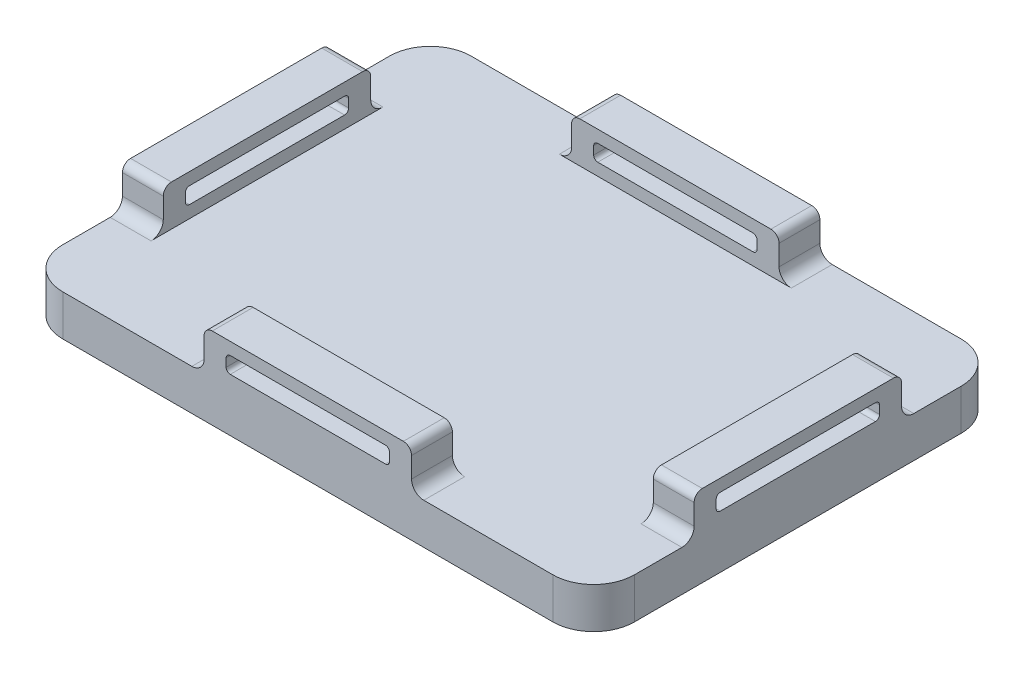
SolidWorks part; units mm, degrees
ref_plane "Front Plane" through (0, 0, 0) normal (0, 0, 1) x (1, 0, 0)
ref_plane "Top Plane" through (0, 0, 0) normal (0, 1, 0) x (1, 0, 0)
ref_plane "Right Plane" through (0, 0, 0) normal (1, 0, 0) x (0, 0, -1)
sketch "Sketch1" plane through (0, 0, 0) normal (0, 1, 0) x (1, 0, 0)
  line L1 (5, 0) -> (65, 0)
  line L2 (0, 5) -> (0, 45)
  line L3 (5, 50) -> (65, 50)
  line L4 (70, 5) -> (70, 45)
  arc A0 (5, 0) -> (0, 5) centre (5, 5) cw
  arc A1 (65, 0) -> (70, 5) centre (65, 5) ccw
  arc A2 (65, 50) -> (70, 45) centre (65, 45) cw
  arc A3 (0, 45) -> (5, 50) centre (5, 45) cw
  point P7 (0, 0)
  point P10 (70, 0)
  point P13 (70, 50)
  dimension "D3" = 5
  dimension "D1" = 70
  dimension "D2" = 50
extrude "Boss-Extrude1" add sketch "Sketch1" along normal blind 5
sketch "Sketch2" plane through (0, 0, 0) normal (0, -1, 0) x (1, 0, 0)
  line L0 (12, -25) -> (15, -25) construction
  line L1 (12, -19) -> (15, -19)
  line L2 (12, -19) -> (12, -31)
  line L3 (12, -31) -> (15, -31)
  line L4 (15, -19) -> (15, -31)
  line L5 (46, -23.5) -> (58, -23.5)
  line L6 (46, -23.5) -> (46, -26.5)
  line L7 (46, -26.5) -> (58, -26.5)
  line L8 (58, -23.5) -> (58, -26.5)
  line L9 (46, -25) -> (58, -25) construction
  line L10 (0, -25) -> (70, -25) construction
  line L11 (0, -45) -> (0, -5) construction
  line L12 (70, -5) -> (70, -45) construction
  dimension "D1" = 12
  dimension "D2" = 3
  dimension "D3" = 12
  dimension "D4" = 3
  dimension "D5" = 12
  dimension "D6" = 12
extrude "Boss-Extrude2" add sketch "Sketch2" along normal blind 10
sketch "Sketch3" plane through (0, 5, 0) normal (0, 1, 0) x (1, 0, 0)
  line L0 (0, 45) -> (0, 5) construction
  line L1 (5, 37.7) -> (0, 37.7)
  line L2 (5, 37.7) -> (5, 12.3)
  line L3 (5, 12.3) -> (0, 12.3)
  line L4 (0, 37.7) -> (0, 12.3)
  line L5 (70, 5) -> (70, 45) construction
  line L6 (70, 37.7) -> (65, 37.7)
  line L7 (70, 37.7) -> (70, 12.3)
  line L8 (70, 12.3) -> (65, 12.3)
  line L9 (65, 37.7) -> (65, 12.3)
  line L10 (0, 25) -> (5, 25) construction
  line L11 (65, 25) -> (70, 25) construction
  line L12 (0, 25) -> (70, 25) construction
  line L13 (65, 50) -> (5, 50) construction
  line L14 (22.3, 50) -> (47.7, 50)
  line L15 (22.3, 50) -> (22.3, 45)
  line L16 (22.3, 45) -> (47.7, 45)
  line L17 (47.7, 50) -> (47.7, 45)
  line L18 (5, 0) -> (65, 0) construction
  line L19 (22.3, 0) -> (47.7, 0)
  line L20 (22.3, 0) -> (22.3, 5)
  line L21 (22.3, 5) -> (47.7, 5)
  line L22 (47.7, 0) -> (47.7, 5)
  line L23 (35, 50) -> (35, 0) construction
  line L24 (35, 5) -> (35, 0) construction
  line L25 (35, 50) -> (35, 45) construction
  dimension "D1" = 25.4
  dimension "D2" = 5
  dimension "D3" = 5
  dimension "D4" = 25.4
  dimension "D5" = 25.4
  dimension "D6" = 25.4
  dimension "D7" = 5
  dimension "D8" = 5
extrude "Boss-Extrude3" add sketch "Sketch3" along normal blind 5
sketch "Sketch4" plane through (0, 0, 0) normal (-1, 0, 0) x (0, 0, 1)
  line L0 (-37.7, 5) -> (-12.3, 5) construction
  line L1 (-37.7, 7.5) -> (-12.3, 7.5) construction
  line L2 (-34.5, 8.5) -> (-15.5, 8.5)
  line L3 (-35, 8) -> (-35, 7)
  line L4 (-34.5, 6.5) -> (-15.5, 6.5)
  line L5 (-15, 8) -> (-15, 7)
  line L6 (-37.7, 10) -> (-37.7, 5) construction
  line L7 (-12.3, 10) -> (-12.3, 5) construction
  line L8 (-35, 7.5) -> (-15, 7.5) construction
  line L9 (-25, 10) -> (-25, 5) construction
  line L10 (-37.7, 10) -> (-12.3, 10) construction
  line L11 (-25, 8.5) -> (-25, 6.5) construction
  arc A0 (-15.5, 8.5) -> (-15, 8) centre (-15.5, 8) cw
  arc A1 (-15.5, 6.5) -> (-15, 7) centre (-15.5, 7) ccw
  arc A2 (-35, 7) -> (-34.5, 6.5) centre (-34.5, 7) ccw
  arc A3 (-34.5, 8.5) -> (-35, 8) centre (-34.5, 8) ccw
  point P22 (-25, 7.5)
  point P23 (-25, 7.5)
  point P26 (-15, 8.5)
  point P31 (-35, 6.5)
  point P34 (-35, 8.5)
  dimension "D3" = 0.5
  dimension "D1" = 20
  dimension "D2" = 2
extrude "Cut-Extrude1" cut sketch "Sketch4" against normal through all
sketch "Sketch5" plane through (0, 0, 0) normal (0, 0, 1) x (1, 0, 0)
  line L0 (22.3, 5) -> (47.7, 5) construction
  line L1 (35, 10) -> (35, 5) construction
  line L2 (22.3, 10) -> (47.7, 10) construction
  line L3 (22.3, 7.5) -> (47.7, 7.5) construction
  line L4 (22.3, 10) -> (22.3, 5) construction
  line L5 (47.7, 10) -> (47.7, 5) construction
  line L6 (35, 8.5) -> (35, 6.5) construction
  line L7 (25.5, 8.5) -> (44.5, 8.5)
  line L8 (25, 8) -> (25, 7)
  line L9 (25.5, 6.5) -> (44.5, 6.5)
  line L10 (45, 8) -> (45, 7)
  line L11 (25, 7.5) -> (45, 7.5) construction
  arc A0 (44.5, 6.5) -> (45, 7) centre (44.5, 7) ccw
  arc A1 (44.5, 8.5) -> (45, 8) centre (44.5, 8) cw
  arc A2 (25, 7) -> (25.5, 6.5) centre (25.5, 7) ccw
  arc A3 (25.5, 8.5) -> (25, 8) centre (25.5, 8) ccw
  point P22 (35, 7.5)
  point P23 (35, 7.5)
  point P28 (45, 8.5)
  point P31 (25, 6.5)
  point P34 (25, 8.5)
  dimension "D3" = 0.5
  dimension "D1" = 20
  dimension "D2" = 2
extrude "Cut-Extrude2" cut sketch "Sketch5" against normal through all
fillet "Fillet1" radius 1 8 edges at (67.5, 10, -37.7) (67.5, 10, -12.3) (2.5, 10, -12.3) (2.5, 10, -37.7) (22.3, 10, -47.5) (47.7, 10, -47.5) (22.3, 10, -2.5) (47.7, 10, -2.5)
fillet "Fillet2" radius 1.5 8 edges at (22.3, 5, -2.5) (47.7, 5, -2.5) (67.5, 5, -12.3) (67.5, 5, -37.7) (47.7, 5, -47.5) (22.3, 5, -47.5) (2.5, 5, -37.7) (2.5, 5, -12.3)
sketch "Sketch6" plane through (12, 0, 0) normal (-1, 0, 0) x (0, 0, 1)
  line L0 (-25, 0) -> (-25, -10) construction
  line L1 (-19, 0) -> (-31, 0) construction
  line L2 (-19, -10) -> (-31, -10) construction
  line L3 (-31, -5) -> (-19, -5) construction
  line L4 (-31, -10) -> (-31, 0) construction
  line L5 (-19, -10) -> (-19, 0) construction
  circle A0 centre (-25, -5) radius 1.5
  dimension "D1" = 3
extrude "Cut-Extrude3" cut sketch "Sketch6" against normal blind 3
sketch "Sketch7" plane through (0, 0, -23.5) normal (0, 0, 1) x (1, 0, 0)
  line L0 (52, 0) -> (52, -10) construction
  line L1 (58, 0) -> (46, 0) construction
  line L2 (58, -10) -> (46, -10) construction
  line L3 (46, -5) -> (58, -5) construction
  line L4 (46, -10) -> (46, 0) construction
  line L5 (58, -10) -> (58, 0) construction
  circle A0 centre (52, -5) radius 1.5
  dimension "D1" = 3
extrude "Cut-Extrude4" cut sketch "Sketch7" against normal blind 3
fillet "Fillet3" radius 1.5 4 edges at (58, -10, -25) (46, -10, -25) (13.5, -10, -19) (13.5, -10, -31)
fillet "Fillet4" radius 1.5 4 edges at (58, 0, -25) (46, 0, -25) (13.5, 0, -19) (13.5, 0, -31)
